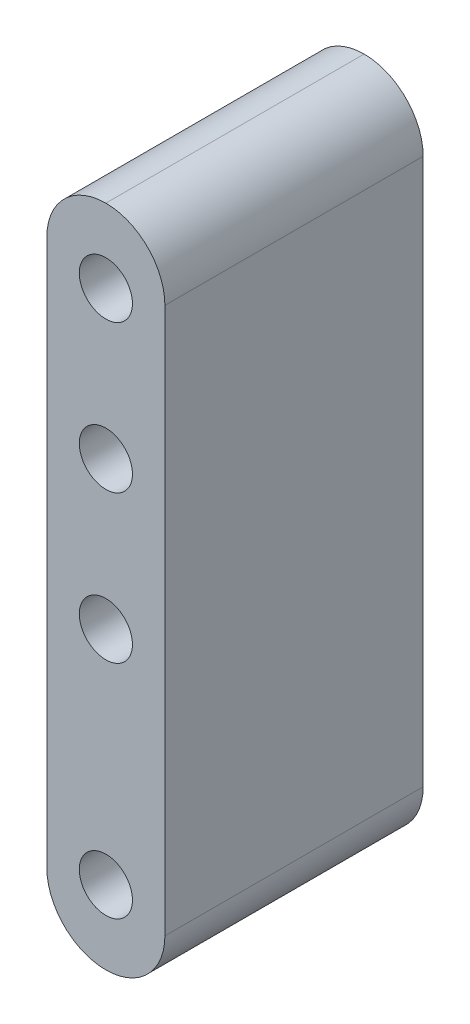
SolidWorks part; units mm, degrees
ref_plane "Front Plane" through (0, 0, 0) normal (0, 0, 1) x (1, 0, 0)
ref_plane "Top Plane" through (0, 0, 0) normal (0, 1, 0) x (1, 0, 0)
ref_plane "Right Plane" through (0, 0, 0) normal (1, 0, 0) x (0, 0, -1)
sketch "Sketch1" plane through (0, 0, 0) normal (0, 0, 1) x (1, 0, 0)
  line L1 (0, 0) -> (10.16, 0)
  line L2 (0, 0) -> (0, 57.15)
  line L3 (0, 57.15) -> (10.16, 57.15)
  line L4 (10.16, 0) -> (10.16, 57.15)
  circle A0 centre (5.08, 6.35) radius 2.286
  circle A1 centre (5.08, 25.4) radius 2.286
  circle A2 centre (5.08, 38.1) radius 2.286
  circle A3 centre (5.08, 50.8) radius 2.286
  dimension "D4" = 4.572
  dimension "D1" = 10.16
  dimension "D2" = 5.08
  dimension "D3" = 6.35
  dimension "D5" = 19.05
  dimension "D7" = 12.7
  dimension "D8" = 6.35
  dimension "D6" = 3
extrude "Boss-Extrude1" add sketch "Sketch1" along normal blind 22.225
fillet "Fillet1" radius 5.08 4 edges at (10.16, 0, 11.1125) (0, 0, 11.1125) (0, 57.15, 11.1125) (10.16, 57.15, 11.1125)
